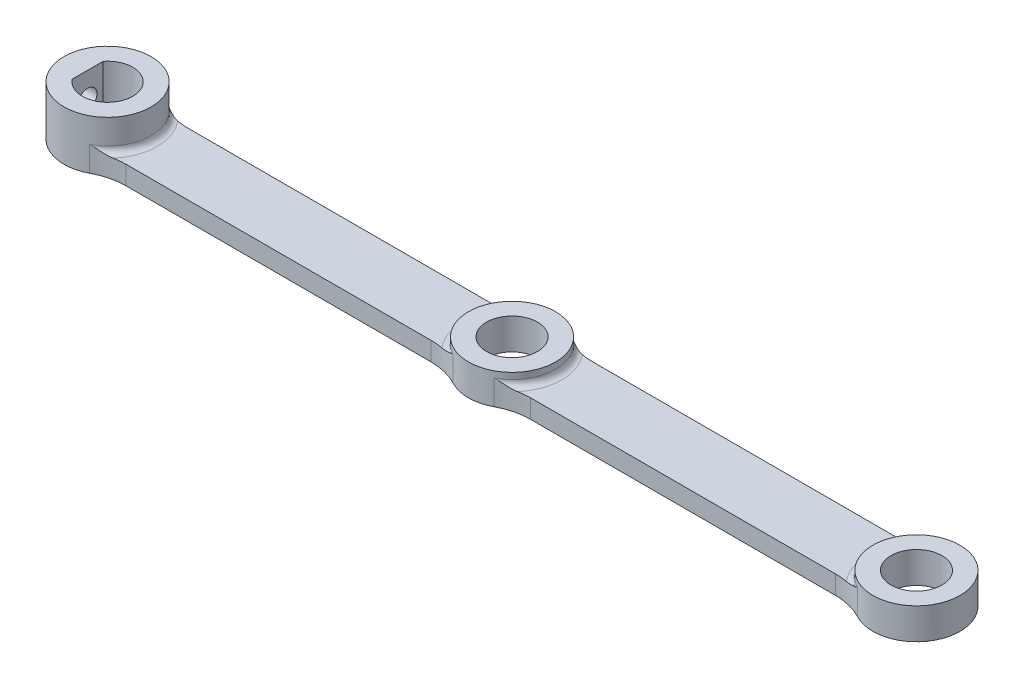
SolidWorks part; units mm, degrees
ref_plane "前视基准面" through (0, 0, 0) normal (0, 0, 1) x (1, 0, 0)
ref_plane "上视基准面" through (0, 0, 0) normal (0, 1, 0) x (1, 0, 0)
ref_plane "右视基准面" through (0, 0, 0) normal (1, 0, 0) x (0, 0, -1)
sketch "Sketch1" plane through (0, 0, 0) normal (0, 1, 0) x (1, 0, 0)
  line L0 (0, 0) -> (130, 0) construction
  line L1 (0, 5) -> (130, 5)
  line L2 (0, -5) -> (130, -5)
  arc A0 (0, 5) -> (0, -5) centre (0, 0) ccw
  arc A1 (130, -5) -> (130, 5) centre (130, 0) ccw
  circle A2 centre (0, 0) radius 1.6
  point P3 (65, 0)
  dimension "D2" = 5
  dimension "D3" = 3.2
  dimension "D1" = 130
extrude "Boss-Extrude1" add sketch "Sketch1" along normal blind 3
sketch "Sketch2" plane through (0, 3, 0) normal (0, 1, 0) x (1, 0, 0)
  circle A0 centre (0, 0) radius 7
  dimension "D1" = 14
extrude "Boss-Extrude2" add sketch "Sketch2" against normal blind 3 and the other way blind 5
sketch "Sketch3" plane through (0, 8, 0) normal (0, 1, 0) x (1, 0, 0)
  line L0 (0, 3.7575) -> (0, -4.7435) construction
  line L1 (-3.2, 2.4824) -> (-3.2, -2.4824)
  line L3 (-3.2, 3.7575) -> (-3.2, -4.7435) construction
  arc A0 (-3.2, -2.4824) -> (-3.2, 2.4824) centre (0, 0) ccw
  dimension "D1" = 8.1
  dimension "D2" = 3.2
extrude "Cut-Extrude1" cut sketch "Sketch3" against normal through all
sketch "Sketch4" plane through (-3.2, 0, 0) normal (1, 0, 0) x (0, 0, -1)
  line L0 (0, 8) -> (0, 4.9157) construction
  line L1 (4.05, 8) -> (-4.05, 8) construction
  circle A0 centre (0, 4) radius 1.5
  dimension "D1" = 3
  dimension "D2" = 4
extrude "Cut-Extrude2" cut sketch "Sketch4" against normal through all
fillet "Fillet1" radius 10 2 edges at (4.899, 1.5, 5) (4.899, 1.5, -5)
fillet "Fillet2" radius 1 1 edges at (7, 3, 0)
sketch "Sketch6" plane through (0, 0, 0) normal (0, -1, 0) x (1, 0, 0)
  line L0 (0, 0) -> (130, 0) construction
  circle A0 centre (65, 0) radius 7
  circle A1 centre (130, 0) radius 7
  dimension "D1" = 14
  dimension "D2" = 14
extrude "Boss-Extrude3" add sketch "Sketch6" against normal blind 5
sketch "Sketch7" plane through (0, 5, 0) normal (0, 1, 0) x (1, 0, 0)
  circle A0 centre (65, 0) radius 4.1
  circle A1 centre (130, 0) radius 4.1
  dimension "D1" = 8.2
  dimension "D2" = 8.2
extrude "Cut-Extrude4" cut sketch "Sketch7" against normal through all
fillet "Fillet3" radius 10 6 edges at (69.899, 1.5, -5) (60.101, 1.5, -5) (125.101, 1.5, -5) (125.101, 1.5, 5) (69.899, 1.5, 5) (60.101, 1.5, 5)
fillet "Fillet4" radius 1 3 edges at (72, 3, 0) (123, 3, 0) (58, 3, 0)
